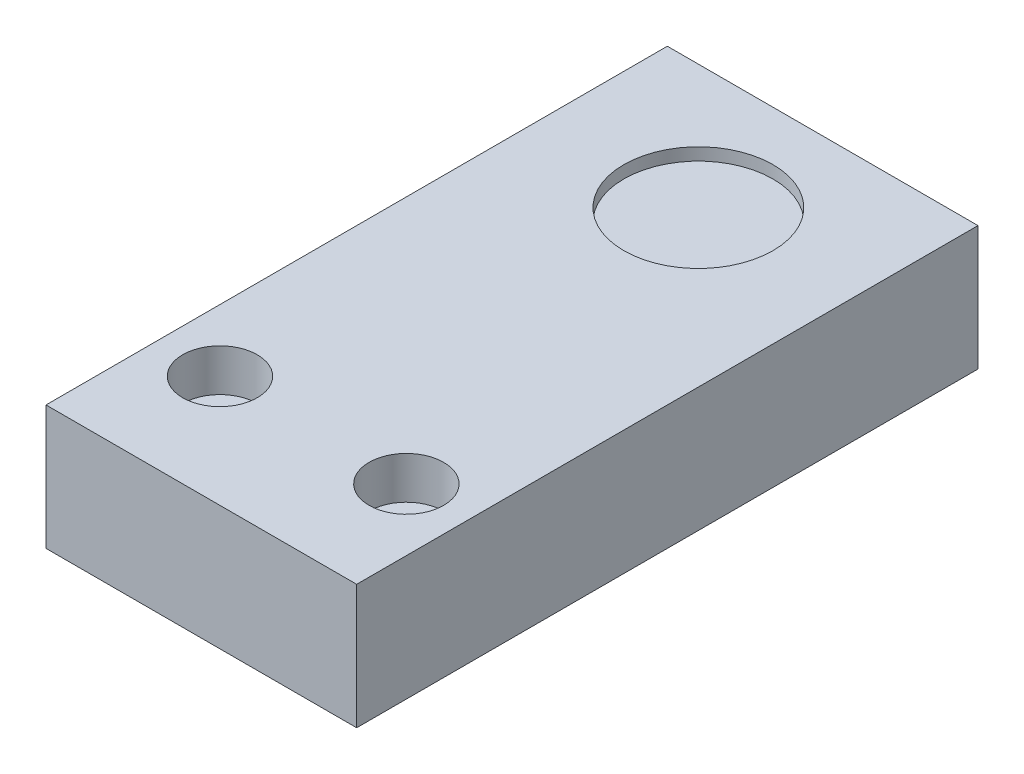
SolidWorks part; units mm, degrees
ref_plane "前视基准面" through (0, 0, 0) normal (0, 0, 1) x (1, 0, 0)
ref_plane "上视基准面" through (0, 0, 0) normal (0, 1, 0) x (1, 0, 0)
ref_plane "右视基准面" through (0, 0, 0) normal (1, 0, 0) x (0, 0, -1)
sketch "草图1" plane through (0, 0, 0) normal (0, 1, 0) x (1, 0, 0)
  line L1 (-12.5, -25) -> (12.5, -25)
  line L2 (-12.5, -25) -> (-12.5, 25)
  line L3 (-12.5, 25) -> (12.5, 25)
  line L4 (12.5, -25) -> (12.5, 25)
  line L5 (-12.5, -25) -> (12.5, 25) construction
  line L6 (-12.5, 25) -> (12.5, -25) construction
  point P0 (0, 0)
  dimension "D1" = 25
  dimension "D2" = 50
extrude "凸台-拉伸1" add sketch "草图1" along normal blind 10
hole_wizard "打孔尺寸(%根据)内六角圆柱头螺钉的类型1" positions "草图4" profile "草图3" counterbore size "M3" standard "GB" end condition through all
sketch "草图4" plane through (0, 10, 0) normal (0, 1, 0) x (1, 0, 0)
  line L1 (-12.5, -25) -> (12.5, -25) construction
  line L3 (0, 0) -> (0, -29.7046) construction
  point P0 (-7.5, -16)
  point P2 (7.5, -16)
  dimension "D1" = 15
  dimension "D2" = 9
sketch "草图3" plane through (-7.5, 10, 16) normal (1, 0, 0) x (0, 0, 1)
  line L0 (0, 0) -> (0, 10)
  line L1 (0, 10) -> (1.6, 10)
  line L3 (1.6, 10) -> (1.6, 3.4)
  line L4 (1.6, 3.4) -> (3, 3.4)
  line L5 (3, 3.4) -> (3, 0)
  line L7 (3, 0) -> (0, 0)
  line L11 (0, -6.35) -> (0, 107.95) construction
  dimension "通孔孔直径" = 3.2
  dimension "通孔孔深度" = 10
  dimension "柱形沉头孔直径" = 6
  dimension "柱形沉头孔深度" = 3.4
sketch "草图5" plane through (0, 10, 0) normal (0, 1, 0) x (1, 0, 0)
  line L0 (12.5, 25) -> (-12.5, 25) construction
  circle A0 centre (0, 15) radius 6
  dimension "D1" = 12
  dimension "D2" = 10
extrude "切除-拉伸1" cut sketch "草图5" against normal blind 1
